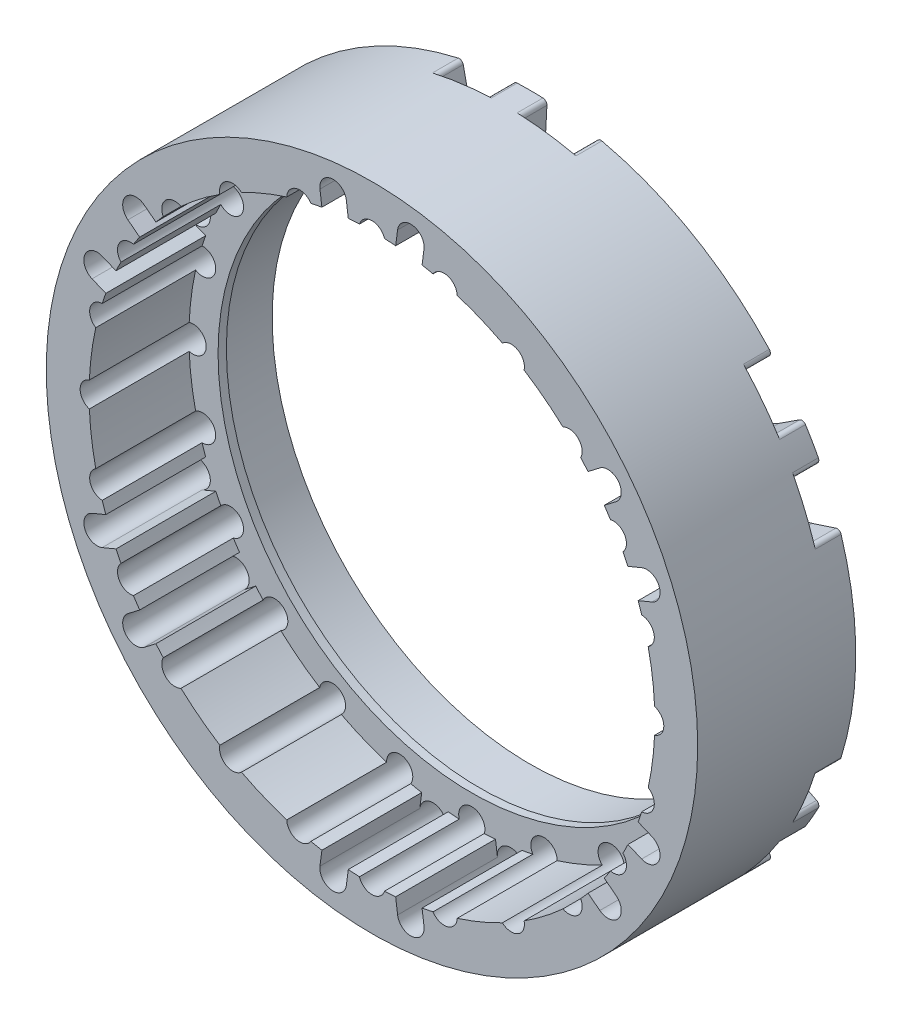
SolidWorks part; units mm, degrees
material "ABS"
ref_plane "Front Plane" through (0, 0, 0) normal (0, 0, 1) x (1, 0, 0)
ref_plane "Top Plane" through (0, 0, 0) normal (0, 1, 0) x (1, 0, 0)
ref_plane "Right Plane" through (0, 0, 0) normal (1, 0, 0) x (0, 0, -1)
sketch "CYC Master Sketch" plane through (0, 0, 0) normal (0, 0, 1) x (1, 0, 0)
  circle A0 centre (0, 0) radius 39.15
  circle A2 centre (0, 0) radius 33.5 construction
  circle A3 centre (-33.5, 0) radius 1.575
  circle A4 centre (-32.3585, 8.6704) radius 1.575
  circle A5 centre (-29.0119, 16.75) radius 1.575
  circle A6 centre (-23.6881, 23.6881) radius 1.575
  circle A7 centre (-16.75, 29.0119) radius 1.575
  circle A8 centre (-8.6704, 32.3585) radius 1.575
  circle A9 centre (0, 33.5) radius 1.575
  circle A10 centre (8.6704, 32.3585) radius 1.575
  circle A11 centre (16.75, 29.0119) radius 1.575
  circle A12 centre (23.6881, 23.6881) radius 1.575
  circle A13 centre (29.0119, 16.75) radius 1.575
  circle A14 centre (32.3585, 8.6704) radius 1.575
  circle A15 centre (33.5, 0) radius 1.575
  circle A16 centre (32.3585, -8.6704) radius 1.575
  circle A17 centre (29.0119, -16.75) radius 1.575
  circle A18 centre (23.6881, -23.6881) radius 1.575
  circle A19 centre (16.75, -29.0119) radius 1.575
  circle A20 centre (8.6704, -32.3585) radius 1.575
  circle A21 centre (0, -33.5) radius 1.575
  circle A22 centre (-8.6704, -32.3585) radius 1.575
  circle A23 centre (0, 0) radius 34
  circle A24 centre (-16.75, -29.0119) radius 1.575
  circle A25 centre (-23.6881, -23.6881) radius 1.575
  circle A26 centre (-29.0119, -16.75) radius 1.575
  circle A27 centre (-32.3585, -8.6704) radius 1.575
  circle A28 centre (0, 0) radius 31 construction
  circle A29 centre (0, 0) radius 24.975 construction
  circle A30 centre (0, 0) radius 35.75 construction
  circle A31 centre (4.6663, -35.4442) radius 1.6
  circle A32 centre (-4.6663, -35.4442) radius 1.6
  circle A33 centre (-28.3624, -21.7632) radius 1.6
  circle A34 centre (-33.0287, -13.6809) radius 1.6
  circle A35 centre (-33.0287, 13.6809) radius 1.6
  circle A36 centre (-28.3624, 21.7632) radius 1.6
  circle A37 centre (-4.6663, 35.4442) radius 1.6
  circle A38 centre (4.6663, 35.4442) radius 1.6
  circle A39 centre (28.3624, 21.7632) radius 1.6
  circle A40 centre (33.0287, 13.6809) radius 1.6
  circle A41 centre (33.0287, -13.6809) radius 1.6
  circle A42 centre (28.3624, -21.7632) radius 1.6
  point P47 (0, 0)
  point P72 (0, 0)
extrude "Gearbox Wall" add sketch "CYC Master Sketch" along normal blind 19 contours A0 A23 A13 A14 A15 A16 A17 A18 A19 A20 A21 A22 A3 A4 A5 A6 A7 A8 A9 A10 A11 A12 region at (-38.0427, 0, 0)
extrude "Gearbox Bottom" add sketch "CYC Master Sketch<3>" along normal blind 7 contours A21 A23 | A23 A20 | A20 A23 | A23 A19 | A19 A23 | A23 A18 | A18 A23 | A23 A17 | A17 A23 | A23 A16 | A16 A23 | A23 A15 | A15 A23 | A23 A14 | A14 A23 | A23 A13 | A13 A23 | A23 A12 | A12 A23 | A23 A11 | A11 A23 | A23 A10 | A10 A23 | A23 A9 | A9 A23 | A23 A8 | A8 A23 | A23 A7 | A7 A23 | A23 A6 | A6 A23 | A23 A5 | A5 A23 | A23 A4 | A4 A23 | A23 A3 | A3 A23 | A23 A22 | A22 A23 | A13 A23 A12 A11 A10 A9 A8 A7 A6 A5 A4 A3 A22 A21 A20 A19 A18 A17 A16 A15 A14 | A24 | A25 | A26 | A27 | A21 region at (-33.0866, 0, 0) region at (0, 0, 0) region at (-34.4394, 0, 0) region at (-31.9592, 8.5634, 0) region at (-33.2659, 8.9136, 0) region at (-28.6538, 16.5433, 0) region at (-29.8254, 17.2197, 0) region at (-23.3958, 23.3958, 0) region at (-24.3523, 24.3523, 0) region at (-16.5433, 28.6538, 0) region at (-17.2197, 29.8254, 0) region at (-8.5634, 31.9592, 0) region at (-8.9136, 33.2659, 0) region at (-8.9136, -33.2659, 0) region at (-8.5634, -31.9592, 0) region at (0, 33.0866, 0) region at (0, 34.4394, 0) region at (0, -33.0866, 0) region at (8.5634, 31.9592, 0) region at (8.9136, 33.2659, 0) region at (8.9136, -33.2659, 0) region at (8.5634, -31.9592, 0) region at (16.5433, 28.6538, 0) region at (17.2197, 29.8254, 0) region at (17.2197, -29.8254, 0) region at (16.5433, -28.6538, 0) region at (23.3958, 23.3958, 0) region at (24.3523, 24.3523, 0) region at (24.3523, -24.3523, 0) region at (23.3958, -23.3958, 0) region at (28.6538, 16.5433, 0) region at (29.8254, 17.2197, 0) region at (29.8254, -17.2197, 0) region at (28.6538, -16.5433, 0) region at (31.9592, 8.5634, 0) region at (33.2659, 8.9136, 0) region at (33.2659, -8.9136, 0) region at (31.9592, -8.5634, 0) region at (33.0866, 0, 0) region at (34.4394, 0, 0)
sketch "CYC Master Sketch<3>" plane through (0, 0, 0) normal (0, 0, 1) x (1, 0, 0) same geometry as "CYC Master Sketch"
extrude "Pin Cut" cut sketch "CYC Master Sketch<2>" against normal blind 4 from surface contours A23 A7 | A7 A23 | A23 A6 | A6 A23 | A23 A5 | A5 A23 | A23 A4 | A4 A23 | A23 A3 | A3 A23 | A23 A22 | A22 A23 | A23 A21 | A21 A23 | A23 A20 | A20 A23 | A23 A19 | A19 A23 | A23 A18 | A18 A23 | A23 A17 | A17 A23 | A16 A23 | A23 A16 | A15 A23 | A23 A15 | A23 A14 | A14 A23 | A23 A13 | A13 A23 | A23 A12 | A12 A23 | A23 A11 | A11 A23 | A10 A23 | A23 A9 | A9 A23 | A23 A8 | A8 A23 | A23 A10 | A23 A24 | A23 A24 | A23 A25 | A23 A25 | A23 A26 | A23 A26 | A23 A27 | A23 A27 region at (-33.0866, 0, 0) region at (-34.4394, 0, 0) region at (-31.9592, 8.5634, 0) region at (-33.2659, 8.9136, 0) region at (-31.9592, -8.5634, 0) region at (-33.2659, -8.9136, 0) region at (-28.6538, 16.5433, 0) region at (-29.8254, 17.2197, 0) region at (-28.6538, -16.5433, 0) region at (-29.8254, -17.2197, 0) region at (-23.3958, 23.3958, 0) region at (-24.3523, 24.3523, 0) region at (-23.3958, -23.3958, 0) region at (-24.3523, -24.3523, 0) region at (-16.5433, 28.6538, 0) region at (-17.2197, 29.8254, 0) region at (-16.5433, -28.6538, 0) region at (-17.2197, -29.8254, 0) region at (-8.5634, 31.9592, 0) region at (-8.9136, 33.2659, 0) region at (-8.9136, -33.2659, 0) region at (-8.5634, -31.9592, 0) region at (0, 33.0866, 0) region at (0, 34.4394, 0) region at (0, -34.4394, 0) region at (0, -33.0866, 0) region at (8.5634, 31.9592, 0) region at (8.9136, 33.2659, 0) region at (8.9136, -33.2659, 0) region at (8.5634, -31.9592, 0) region at (16.5433, 28.6538, 0) region at (17.2197, 29.8254, 0) region at (17.2197, -29.8254, 0) region at (16.5433, -28.6538, 0) region at (23.3958, 23.3958, 0) region at (24.3523, 24.3523, 0) region at (24.3523, -24.3523, 0) region at (23.3958, -23.3958, 0) region at (28.6538, 16.5433, 0) region at (29.8254, 17.2197, 0) region at (29.8254, -17.2197, 0) region at (28.6538, -16.5433, 0) region at (31.9592, 8.5634, 0) region at (33.2659, 8.9136, 0) region at (33.2659, -8.9136, 0) region at (31.9592, -8.5634, 0) region at (33.0866, 0, 0) region at (34.4394, 0, 0) starting at face at (0, 0, 7)
sketch "CYC Master Sketch<2>" plane through (0, 0, 0) normal (0, 0, 1) x (1, 0, 0) same geometry as "CYC Master Sketch"
sketch "CYC Master" plane through (0, 0, 7) normal (0, 0, 1) x (1, 0, 0)
  circle A0 centre (0, 0) radius 39.15
  circle A2 centre (0, 0) radius 33.5 construction
  circle A3 centre (-33.5, 0) radius 1.575
  circle A4 centre (-32.3585, 8.6704) radius 1.575
  circle A5 centre (-29.0119, 16.75) radius 1.575
  circle A6 centre (-23.6881, 23.6881) radius 1.575
  circle A7 centre (-16.75, 29.0119) radius 1.575
  circle A8 centre (-8.6704, 32.3585) radius 1.575
  circle A9 centre (0, 33.5) radius 1.575
  circle A10 centre (8.6704, 32.3585) radius 1.575
  circle A11 centre (16.75, 29.0119) radius 1.575
  circle A12 centre (23.6881, 23.6881) radius 1.575
  circle A13 centre (29.0119, 16.75) radius 1.575
  circle A14 centre (32.3585, 8.6704) radius 1.575
  circle A15 centre (33.5, 0) radius 1.575
  circle A16 centre (32.3585, -8.6704) radius 1.575
  circle A17 centre (29.0119, -16.75) radius 1.575
  circle A18 centre (23.6881, -23.6881) radius 1.575
  circle A19 centre (16.75, -29.0119) radius 1.575
  circle A20 centre (8.6704, -32.3585) radius 1.575
  circle A21 centre (0, -33.5) radius 1.575
  circle A22 centre (-8.6704, -32.3585) radius 1.575
  circle A23 centre (0, 0) radius 34
  circle A24 centre (-16.75, -29.0119) radius 1.575
  circle A25 centre (-23.6881, -23.6881) radius 1.575
  circle A26 centre (-29.0119, -16.75) radius 1.575
  circle A27 centre (-32.3585, -8.6704) radius 1.575
  circle A28 centre (0, 0) radius 31 construction
  circle A29 centre (0, 0) radius 24.975 construction
  circle A30 centre (0, 0) radius 35.75 construction
  circle A31 centre (4.6663, -35.4442) radius 1.6
  circle A32 centre (-4.6663, -35.4442) radius 1.6
  circle A33 centre (-28.3624, -21.7632) radius 1.6
  circle A34 centre (-33.0287, -13.6809) radius 1.6
  circle A35 centre (-33.0287, 13.6809) radius 1.6
  circle A36 centre (-28.3624, 21.7632) radius 1.6
  circle A37 centre (-4.6663, 35.4442) radius 1.6
  circle A38 centre (4.6663, 35.4442) radius 1.6
  circle A39 centre (28.3624, 21.7632) radius 1.6
  circle A40 centre (33.0287, 13.6809) radius 1.6
  circle A41 centre (33.0287, -13.6809) radius 1.6
  circle A42 centre (28.3624, -21.7632) radius 1.6
  point P47 (0, 0)
  point P72 (0, 0)
sketch "Sketch2" plane through (0, 0, 7) normal (0, 0, 1) x (1, 0, 0)
  circle A0 centre (0, 0) radius 31
  circle A1 centre (0, 0) radius 31 construction
extrude "Housing Bearing Cut" cut sketch "Sketch2" against normal through all
sketch "Sketch3" plane through (0, 0, 7) normal (0, 0, 1) x (1, 0, 0)
  circle A0 centre (0, 0) radius 31
  circle A1 centre (0, 0) radius 30.5
  circle A2 centre (0, 0) radius 31 construction
  dimension "D1" = 61
  dimension "Housing Bearing Outer (Driven)" = 62
extrude "Housing Bearing Retainer" add sketch "Sketch3" against normal blind 0.5
sketch "Sketch5" plane through (0, 0, 0) normal (0, 0, -1) x (-1, 0, 0)
  line L0 (0, 0) -> (31.7579, 16.1759) construction
  line L1 (0, 0) -> (33.8943, 11.0181) construction
  line L2 (33.8943, 11.0181) -> (37.2322, 12.1031)
  line L3 (31.7579, 16.1759) -> (34.8854, 17.7689)
  line L4 (0, 0) -> (33.9049, 19.575) construction
  line L5 (26.4891, 23.8443) -> (29.0977, 26.1925)
  line L6 (29.8877, 19.4152) -> (32.831, 21.3271)
  line L7 (33.8943, -11.0181) -> (37.2322, -12.1031)
  line L8 (31.7579, -16.1759) -> (34.8854, -17.7689)
  line L9 (26.4891, -23.8443) -> (29.0977, -26.1925)
  line L10 (29.8877, -19.4152) -> (32.831, -21.3271)
  line L11 (7.4052, -34.8624) -> (8.1345, -38.2956)
  line L12 (1.8702, -35.5911) -> (2.0543, -39.0961)
  line L13 (-7.4052, -34.8624) -> (-8.1345, -38.2956)
  line L14 (-1.8702, -35.5911) -> (-2.0543, -39.0961)
  line L15 (-26.4891, -23.8443) -> (-29.0977, -26.1925)
  line L16 (-29.8877, -19.4152) -> (-32.831, -21.3271)
  line L17 (-33.8943, -11.0181) -> (-37.2322, -12.1031)
  line L18 (-31.7579, -16.1759) -> (-34.8854, -17.7689)
  line L19 (-33.8943, 11.0181) -> (-37.2322, 12.1031)
  line L20 (-31.7579, 16.1759) -> (-34.8854, 17.7689)
  line L21 (-26.4891, 23.8443) -> (-29.0977, 26.1925)
  line L22 (-29.8877, 19.4152) -> (-32.831, 21.3271)
  line L23 (-7.4052, 34.8624) -> (-8.1345, 38.2956)
  line L24 (-1.8702, 35.5911) -> (-2.0543, 39.0961)
  line L25 (7.4052, 34.8624) -> (8.1345, 38.2956)
  line L26 (1.8702, 35.5911) -> (2.0543, 39.0961)
  arc A0 (31.7579, 16.1759) -> (33.8943, 11.0181) centre (33.0287, 13.6809) ccw
  arc A1 (-32.831, -21.3271) -> (-29.0977, -26.1925) centre (0, 0) ccw
  circle A2 centre (0, 0) radius 39.15 construction
  arc A3 (34.8854, 17.7689) -> (37.2322, 12.1031) centre (0, 0) cw
  arc A4 (32.831, 21.3271) -> (29.0977, 26.1925) centre (0, 0) ccw
  arc A5 (29.8877, 19.4152) -> (26.4891, 23.8443) centre (28.3624, 21.7632) cw
  arc A6 (34.8854, -17.7689) -> (37.2322, -12.1031) centre (0, 0) ccw
  arc A7 (31.7579, -16.1759) -> (33.8943, -11.0181) centre (33.0287, -13.6809) cw
  arc A8 (32.831, -21.3271) -> (29.0977, -26.1925) centre (0, 0) cw
  arc A9 (29.8877, -19.4152) -> (26.4891, -23.8443) centre (28.3624, -21.7632) ccw
  arc A10 (2.0543, -39.0961) -> (8.1345, -38.2956) centre (0, 0) ccw
  arc A11 (1.8702, -35.5911) -> (7.4052, -34.8624) centre (4.6663, -35.4442) cw
  arc A12 (-2.0543, -39.0961) -> (-8.1345, -38.2956) centre (0, 0) cw
  arc A13 (-1.8702, -35.5911) -> (-7.4052, -34.8624) centre (-4.6663, -35.4442) ccw
  arc A14 (-29.8877, -19.4152) -> (-26.4891, -23.8443) centre (-28.3624, -21.7632) cw
  arc A15 (-34.8854, -17.7689) -> (-37.2322, -12.1031) centre (0, 0) cw
  arc A16 (-31.7579, -16.1759) -> (-33.8943, -11.0181) centre (-33.0287, -13.6809) ccw
  arc A17 (-34.8854, 17.7689) -> (-37.2322, 12.1031) centre (0, 0) ccw
  arc A18 (-31.7579, 16.1759) -> (-33.8943, 11.0181) centre (-33.0287, 13.6809) cw
  arc A19 (-32.831, 21.3271) -> (-29.0977, 26.1925) centre (0, 0) cw
  arc A20 (-29.8877, 19.4152) -> (-26.4891, 23.8443) centre (-28.3624, 21.7632) ccw
  arc A21 (-2.0543, 39.0961) -> (-8.1345, 38.2956) centre (0, 0) ccw
  arc A22 (-1.8702, 35.5911) -> (-7.4052, 34.8624) centre (-4.6663, 35.4442) cw
  arc A23 (2.0543, 39.0961) -> (8.1345, 38.2956) centre (0, 0) cw
  arc A24 (1.8702, 35.5911) -> (7.4052, 34.8624) centre (4.6663, 35.4442) ccw
  point P39 (0, 0)
  dimension "D1" = 5.6
  dimension "D3" = 6
  dimension "D2" = 7.5
extrude "M3 Socket Head Cutout" cut sketch "Sketch5" against normal blind 3.1
fillet "Fillet1" radius 0.5 24 edges at (-8.1345, -38.2956, 1.55) (-2.0543, -39.0961, 1.55) (2.0543, -39.0961, 1.55) (8.1345, -38.2956, 1.55) (-29.0977, -26.1925, 1.55) (-32.831, -21.3271, 1.55) (-37.2322, -12.1031, 1.55) (-34.8854, -17.7689, 1.55) (-29.0977, 26.1925, 1.55) (-32.831, 21.3271, 1.55) (-34.8854, 17.7689, 1.55) (-37.2322, 12.1031, 1.55) (-8.1345, 38.2956, 1.55) (-2.0543, 39.0961, 1.55) (8.1345, 38.2956, 1.55) (2.0543, 39.0961, 1.55) (29.0977, 26.1925, 1.55) (32.831, 21.3271, 1.55) (34.8854, 17.7689, 1.55) (37.2322, 12.1031, 1.55) (37.2322, -12.1031, 1.55) (34.8854, -17.7689, 1.55) (32.831, -21.3271, 1.55) (29.0977, -26.1925, 1.55)
sketch "Sketch6" plane through (0, 0, 19) normal (0, 0, 1) x (1, 0, 0)
  line L0 (-6.0193, 33.4629) -> (-6.2526, 35.2353)
  line L1 (-2.8467, 33.8806) -> (-3.08, 35.653)
  line L2 (0, 0) -> (-4.6663, 35.4442) construction
  line L3 (-6.0193, 33.4629) -> (-2.8467, 33.8806)
  line L4 (2.8467, 33.8806) -> (3.08, 35.653)
  line L5 (6.0193, 33.4629) -> (6.2526, 35.2353)
  line L6 (2.8467, 33.8806) -> (6.0193, 33.4629)
  line L7 (0, 0) -> (4.6663, 35.4442) construction
  line L8 (0, 0) -> (-2.8467, 33.8806) construction
  line L9 (0, 0) -> (6.0193, 33.4629) construction
  arc A0 (-1.5043, 33.9667) -> (-7.3382, 33.1987) centre (0, 0) ccw construction
  circle A1 centre (-4.6663, 35.4442) radius 1.6 construction
  arc A2 (-3.08, 35.653) -> (-6.2526, 35.2353) centre (-4.6663, 35.4442) ccw
  arc A3 (6.2526, 35.2353) -> (3.08, 35.653) centre (4.6663, 35.4442) ccw
  dimension "D1" = 2
  dimension "D2" = 15
  dimension "D3" = 34
extrude "Cut-Extrude1" cut sketch "Sketch6" against normal up to surface (12 mm away) contours A2 L0 L3 L1 | L4 A3 L5 L6 up to face at (0, 0, 7)
pattern_circular "CirPattern1" count 6 over 360 about axis through (0, 0, 0) along (0, 0, 1) of "Cut-Extrude1", "Housing Bearing Cut"
sketch "Sketch7" plane through (0, 0, 7) normal (0, 0, 1) x (1, 0, 0)
  circle A0 centre (0, 0) radius 31
  circle A1 centre (0, 0) radius 31 construction
  circle A2 centre (0, 0) radius 30.5
  dimension "D1" = 61
extrude "Boss-Extrude1" add sketch "Sketch7" against normal blind 1
